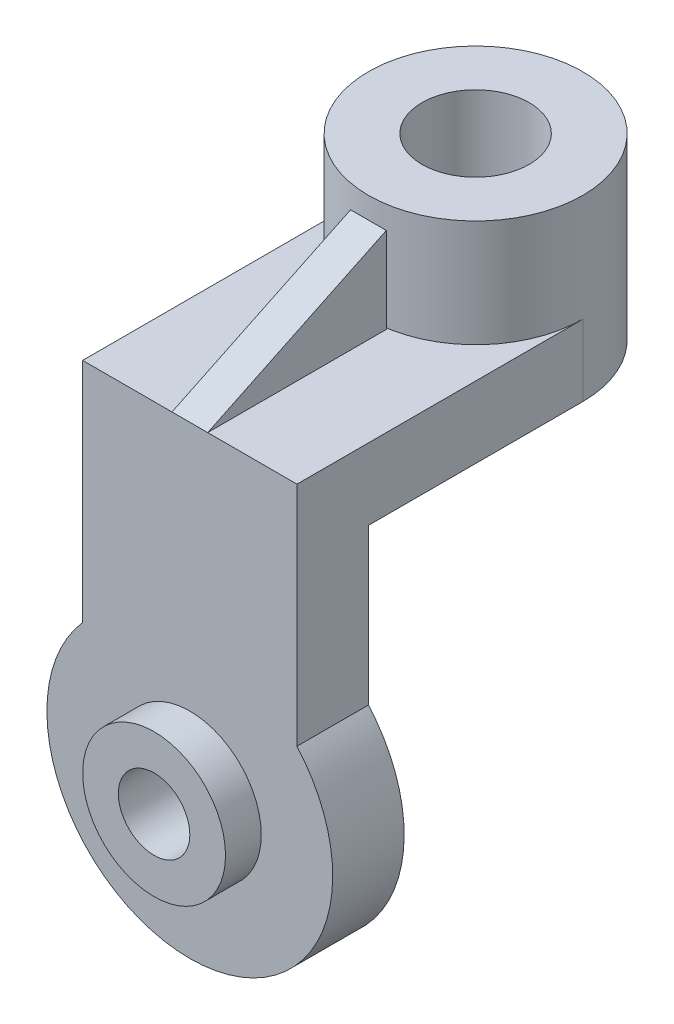
SolidWorks part; units mm, degrees
ref_plane "前视基准面" through (0, 0, 0) normal (0, 0, 1) x (1, 0, 0)
ref_plane "上视基准面" through (0, 0, 0) normal (0, 1, 0) x (1, 0, 0)
ref_plane "右视基准面" through (0, 0, 0) normal (1, 0, 0) x (0, 0, -1)
other "Configuration Table"
sketch "草图1" plane through (0, 0, 0) normal (0, 0, 1) x (1, 0, 0)
  line L0 (0, 0) -> (30, 0)
  line L1 (30, 0) -> (30, -21.7712)
  line L2 (0, 0) -> (0, -21.7712)
  line L3 (15, 0) -> (15, -67.7158) construction
  circle A0 centre (15, -35) radius 5
  circle A1 centre (15, -35) radius 10
  circle A2 centre (15, -35) radius 20
  dimension "D2" = 40
  dimension "D3" = 20
  dimension "D4" = 10
  dimension "D1" = 30
  dimension "D5" = 35
extrude "凸台-拉伸1" add sketch "草图1" along normal blind 10 contours L3 L0 L2 A2 | L0 L3 A2 L1 | A2 L3 A1 | L3 A2 A1 region at (7.0268, -8.6505, 0) region at (22.9732, -8.6505, 0) region at (6.9552, -17.1789, 0) region at (23.0448, -17.1789, 0)
extrude "凸台-拉伸2" add sketch "草图1<3>" along normal blind 15 and the other way blind 5 contours L3 A1 A0 | A1 L3 A0 region at (21.913, -28.087, 0) region at (14.7764, -27.5, 0)
sketch "草图1<3>" plane through (0, 0, 0) normal (0, 0, 1) x (1, 0, 0) same geometry as "草图1"
sketch "草图2" plane through (0, 0, 0) normal (0, 1, 0) x (1, 0, 0)
  line L0 (0, -10) -> (0, 30)
  line L1 (30, -10) -> (30, 30)
  circle A0 centre (15, 30) radius 15
  circle A1 centre (15, 30) radius 7.5
  line M4 (30, 0) -> (0, 0)
  line M5 (0, 0) -> (0, -10)
  line M6 (0, -10) -> (30, -10)
  line M7 (30, -10) -> (30, 0)
  dimension "D2" = 15
  dimension "D1" = 40
extrude "凸台-拉伸3" add sketch "草图2" along normal blind 10 contours A0 L0 L1 M4 | M7 M4 M5 M6 region at (15, 0, 5) region at (15, 0, -9.4171)
extrude "凸台-拉伸4" add sketch "草图2<3>" along normal blind 25 contours A0 region at (15, 0, -15.4243)
sketch "草图2<3>" plane through (0, 0, 0) normal (0, 1, 0) x (1, 0, 0) same geometry as "草图2"
ref_plane "基准面1" through (15, 0, 0) normal (1, 0, 0) x (0, 0, -1)
sketch "草图3" plane through (15, 0, 0) normal (1, 0, 0) x (0, 0, -1)
  line L0 (15, 22) -> (15, 10)
  line L1 (15, 25) -> (15, 10) construction
  line L2 (15, 10) -> (-10, 10)
  line L3 (-10, 10) -> (15, 22)
  line L4 (45, 25) -> (15, 25) construction
  line L5 (15, 10) -> (-10, 10)
  dimension "D2" = 3
extrude "凸台-拉伸6" add sketch "草图3" along normal mid plane 5 separate body contours L3 L2 L0 region at (15, 14, -6.6667)
